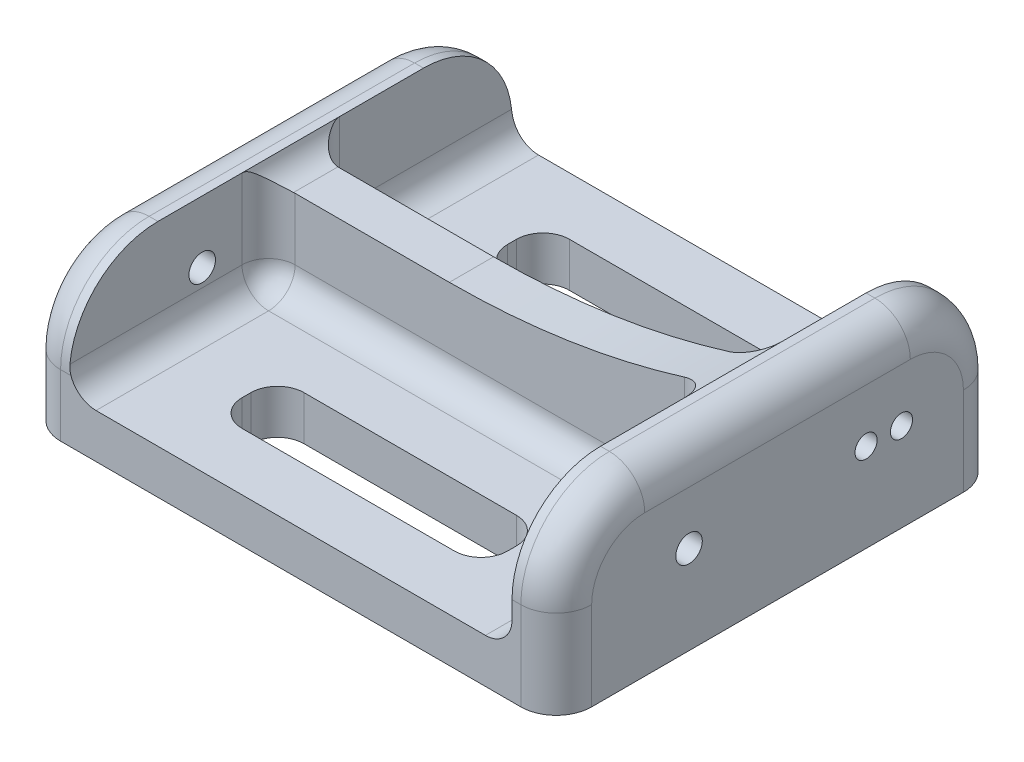
SolidWorks part; units mm, degrees
ref_plane "Front Plane" through (0, 0, 0) normal (0, 0, 1) x (1, 0, 0)
ref_plane "Top Plane" through (0, 0, 0) normal (0, 1, 0) x (1, 0, 0)
ref_plane "Right Plane" through (0, 0, 0) normal (1, 0, 0) x (0, 0, -1)
sketch "Sketch1" plane through (0, 0, 0) normal (0, 1, 0) x (1, 0, 0)
  line L1 (0, 0) -> (60, 0)
  line L2 (0, 0) -> (0, -50)
  line L3 (0, -50) -> (60, -50)
  line L4 (60, 0) -> (60, -50)
  line L5 (0, 0) -> (60, -50) construction
  line L6 (0, -50) -> (60, 0) construction
  point P4 (30, -25)
  dimension "20" = 60
  dimension "D2" = 50
extrude "Boss-Extrude1" add sketch "Sketch1" along normal blind 20
sketch "Sketch2" plane through (0, 20, 0) normal (0, 1, 0) x (1, 0, 0)
  line L0 (0, 0) -> (0, -50) construction
  line L1 (0, 0) -> (55, 0)
  line L2 (0, 0) -> (0, -50)
  line L3 (0, -50) -> (55, -50)
  line L4 (55, 0) -> (55, -50)
  line L5 (0, 0) -> (55, -50) construction
  line L6 (0, -50) -> (55, 0) construction
  line L7 (60, 0) -> (0, 0) construction
  line L8 (0, -50) -> (60, -50) construction
  line L9 (60, -50) -> (60, 0) construction
  point P4 (27.5, -25)
  dimension "D1" = 5
  dimension "D2" = 0
  dimension "D3" = 0
extrude "Cut-Extrude1" cut sketch "Sketch2" against normal blind 15
sketch "Sketch12" plane through (0, 5, 0) normal (0, 1, 0) x (1, 0, 0)
  line L0 (0, -50) -> (55, -50) construction
  line L1 (0, 0) -> (5, 0)
  line L2 (0, 0) -> (0, -50)
  line L3 (0, -50) -> (5, -50)
  line L4 (5, 0) -> (5, -50)
  line L5 (0, 0) -> (5, -50) construction
  line L6 (0, -50) -> (5, 0) construction
  point P4 (2.5, -25)
  dimension "D1" = 5
extrude "Boss-Extrude2" add sketch "Sketch12" along normal blind 12
sketch "Sketch3" plane through (60, 0, 0) normal (1, 0, 0) x (0, 0, -1)
  line L0 (-50, 20) -> (0, 20) construction
  line L2 (-50, 20) -> (-50, 0) construction
  circle A0 centre (-35, 10) radius 1.5
  dimension "D1" = 3
  dimension "D2" = 10
  dimension "D3" = 15
extrude "Cut-Extrude2" cut sketch "Sketch3" against normal through all
sketch "Sketch6" plane through (60, 0, 0) normal (1, 0, 0) x (0, 0, -1)
  line L0 (-50, 20) -> (-50, 0) construction
  circle A0 centre (-15, 10) radius 1.25
  circle A1 centre (-11, 10) radius 1.25
  dimension "D1" = 2.5
  dimension "D2" = 2.5
  dimension "D4" = 4
  dimension "D3" = 35
extrude "Cut-Extrude4" cut sketch "Sketch6" against normal blind 16
fillet "Fillet3" radius 10 1 edges at (57.5, 20, 50)
fillet "Fillet4" radius 10 1 edges at (2.5, 17, 50)
fillet "Fillet5" radius 10 2 edges at (57.5, 20, 0) (2.5, 17, 0)
sketch "Sketch13" plane through (0, 5, 0) normal (0, 1, 0) x (1, 0, 0)
  line L0 (5, -25) -> (5, -22.5)
  line L1 (5, -50) -> (5, 0) construction
  line L2 (5, -22.5) -> (55, -22.5)
  line L3 (55, -40) -> (55, -10) construction
  line L4 (55, -22.5) -> (55, -27.5)
  line L5 (55, -27.5) -> (5, -27.5)
  line L6 (5, -40) -> (5, -10) construction
  line L7 (5, -27.5) -> (5, -25)
  dimension "D1" = 2.5
  dimension "D2" = 2.5
extrude "Boss-Extrude3" add sketch "Sketch13" along normal blind 10
fillet "Fillet7" radius 90 1 edges at (55, 15, 25)
fillet "Fillet8" radius 3 1 edges at (55, 5, 11.25)
fillet "Fillet9" radius 3 11 edges at (55, 14, 22.5) (54.1213, 5.8787, 22.5) (5, 10, 22.5) (5, 10, 27.5) (5, 15, 25) (55, 12.5, 27.5) (30, 5, 27.5) (28.5, 5, 22.5) (5, 5, 11.25) (5, 5, 38.75) (55, 5, 38.75)
sketch "Sketch14" plane through (0, 5, 0) normal (0, 1, 0) x (1, 0, 0)
  line L0 (52, 0) -> (8, 0) construction
  line L1 (15, -6.5) -> (45, -6.5)
  line L2 (15, -6.5) -> (15, -13.5)
  line L3 (15, -13.5) -> (45, -13.5)
  line L4 (45, -6.5) -> (45, -13.5)
  line L5 (15, -6.5) -> (45, -13.5) construction
  line L6 (15, -13.5) -> (45, -6.5) construction
  line L7 (15, -36.5) -> (45, -36.5)
  line L8 (15, -36.5) -> (15, -43.5)
  line L9 (15, -43.5) -> (45, -43.5)
  line L10 (45, -36.5) -> (45, -43.5)
  line L11 (15, -36.5) -> (45, -43.5) construction
  line L12 (15, -43.5) -> (45, -36.5) construction
  line L15 (8, -50) -> (52, -50) construction
  line L17 (52, -50) -> (52, -30.5) construction
  point P0 (30, -10)
  point P5 (30, -40)
  dimension "D1" = 10
  dimension "D2" = 10
  dimension "D3" = 30
  dimension "D4" = 7
  dimension "D5" = 7
  dimension "D6" = 30
  dimension "D8" = 22
extrude "Cut-Extrude8" cut sketch "Sketch14" against normal blind 12
fillet "Fillet10" radius 3 8 edges at (45, 2.5, 43.5) (45, 2.5, 36.5) (15, 2.5, 43.5) (15, 2.5, 36.5) (15, 2.5, 13.5) (45, 2.5, 13.5) (45, 2.5, 6.5) (15, 2.5, 6.5)
fillet "Fillet11" radius 4 5 edges at (60, 5, 50) (60, 17.0711, 47.0711) (60, 20, 25) (60, 17.0711, 2.9289) (60, 5, 0)
fillet "Fillet12" radius 4 5 edges at (0, 3.5, 0) (0, 14.0711, 2.9289) (0, 17, 25) (0, 14.0711, 47.0711) (0, 3.5, 50)
sketch "Sketch15" plane through (0, 5, 0) normal (0, 1, 0) x (1, 0, 0)
  line L0 (5, -10) -> (5, -0.0501) construction
  line L1 (55, 0) -> (55, -10) construction
  line L2 (56, 0) -> (4, 0) construction
  line L3 (52, 0) -> (8, 0) construction
  line L5 (25.4196, -25) -> (29.6663, -25) construction
  line L6 (25.4196, -27.5) -> (25.4196, -22.5) construction
  circle A0 centre (17, -2.5) radius 1.5 construction
  circle A1 centre (43, -2.5) radius 1.5 construction
  circle A2 centre (43, -47.5) radius 1.5 construction
  circle A3 centre (17, -47.5) radius 1.5 construction
  dimension "D2" = 12
  dimension "D5" = 3
  dimension "D6" = 3
  dimension "D1" = 12
  dimension "D3" = 2.5
  dimension "D4" = 2.5
